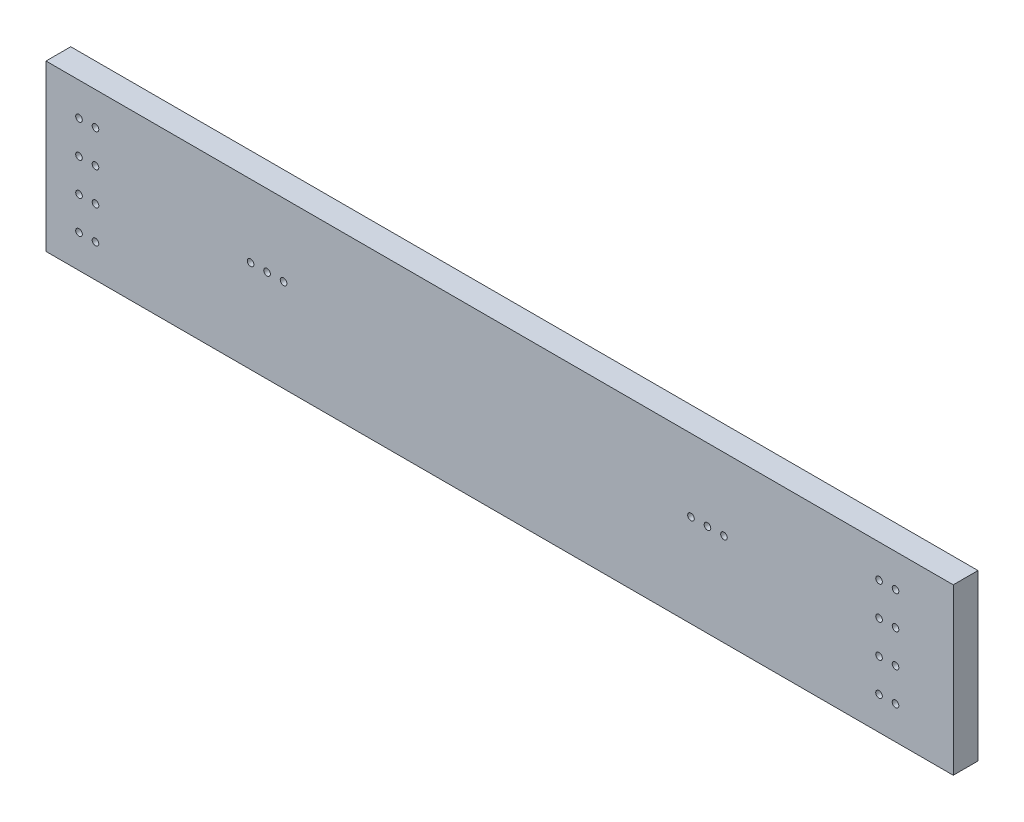
SolidWorks part; units mm, degrees
material "Pine"
ref_plane "Front Plane" through (0, 0, 0) normal (0, 0, 1) x (1, 0, 0)
ref_plane "Top Plane" through (0, 0, 0) normal (0, 1, 0) x (1, 0, 0)
ref_plane "Right Plane" through (0, 0, 0) normal (1, 0, 0) x (0, 0, -1)
sketch "Sketch1" plane through (0, 0, 0) normal (0, 0, 1) x (1, 0, 0)
  line L1 (-349.25, -63.5) -> (349.25, -63.5)
  line L2 (-349.25, -63.5) -> (-349.25, 63.5)
  line L3 (-349.25, 63.5) -> (349.25, 63.5)
  line L4 (349.25, -63.5) -> (349.25, 63.5)
  line L5 (-349.25, -63.5) -> (349.25, 63.5) construction
  line L6 (-349.25, 63.5) -> (349.25, -63.5) construction
  point P0 (0, 0)
  dimension "D1" = 698.5
  dimension "D2" = 127
extrude "Boss-Extrude1" add sketch "Sketch1" along normal blind 19.05
sketch "Sketch2" plane through (0, 0, 19.05) normal (0, 0, 1) x (1, 0, 0)
  line L0 (349.25, -63.5) -> (349.25, 63.5) construction
  line L1 (349.25, 63.5) -> (-349.25, 63.5) construction
  line L2 (-9.525, 63.5) -> (-9.525, -63.5) construction
  line L3 (-349.25, 63.5) -> (-349.25, -63.5) construction
  line L4 (-349.25, 63.5) -> (349.25, 63.5) construction
  line L5 (-349.25, -63.5) -> (349.25, -63.5) construction
  circle A1 centre (304.8, 38.1) radius 2.54
  circle A2 centre (304.8, 12.7) radius 2.54
  circle A3 centre (304.8, -12.7) radius 2.54
  circle A4 centre (304.8, -38.1) radius 2.54
  circle A5 centre (292.1, -38.1) radius 2.54
  circle A6 centre (292.1, -12.7) radius 2.54
  circle A7 centre (292.1, 12.7) radius 2.54
  circle A8 centre (292.1, 38.1) radius 2.54
  circle A9 centre (-323.85, 38.1) radius 2.54
  circle A10 centre (-311.15, 38.1) radius 2.54
  circle A11 centre (-323.85, 12.7) radius 2.54
  circle A12 centre (-311.15, 12.7) radius 2.54
  circle A13 centre (-323.85, -12.7) radius 2.54
  circle A14 centre (-311.15, -12.7) radius 2.54
  circle A15 centre (-323.85, -38.1) radius 2.54
  circle A16 centre (-311.15, -38.1) radius 2.54
  circle A17 centre (147.32, 7.8105) radius 2.54
  circle A18 centre (160.02, 7.8105) radius 2.54
  circle A19 centre (172.72, 7.8105) radius 2.54
  circle A20 centre (-191.77, 7.8105) radius 2.54
  circle A21 centre (-179.07, 7.8105) radius 2.54
  circle A22 centre (-166.37, 7.8105) radius 2.54
  point P58 (0, 0)
  dimension "D1" = 5.08
  dimension "D8" = 5.08
  dimension "D15" = 5.08
  dimension "D21" = 5.08
  dimension "D24" = 339.725
  dimension "D2" = 44.45
  dimension "D3" = 12.7
  dimension "D4" = 25.4
  dimension "D5" = 25.4
  dimension "D6" = 25.4
  dimension "D7" = 25.4
  dimension "D9" = 25.4
  dimension "D10" = 25.4
  dimension "D11" = 25.4
  dimension "D12" = 25.4
  dimension "D13" = 25.4
  dimension "D14" = 12.7
  dimension "D16" = 12.7
  dimension "D17" = 12.7
  dimension "D18" = 313.69
  dimension "D20" = 55.6895
  dimension "D22" = 12.7
  dimension "D23" = 12.7
  dimension "D25" = 156.845
extrude "Cut-Extrude1" cut sketch "Sketch2" against normal through all
